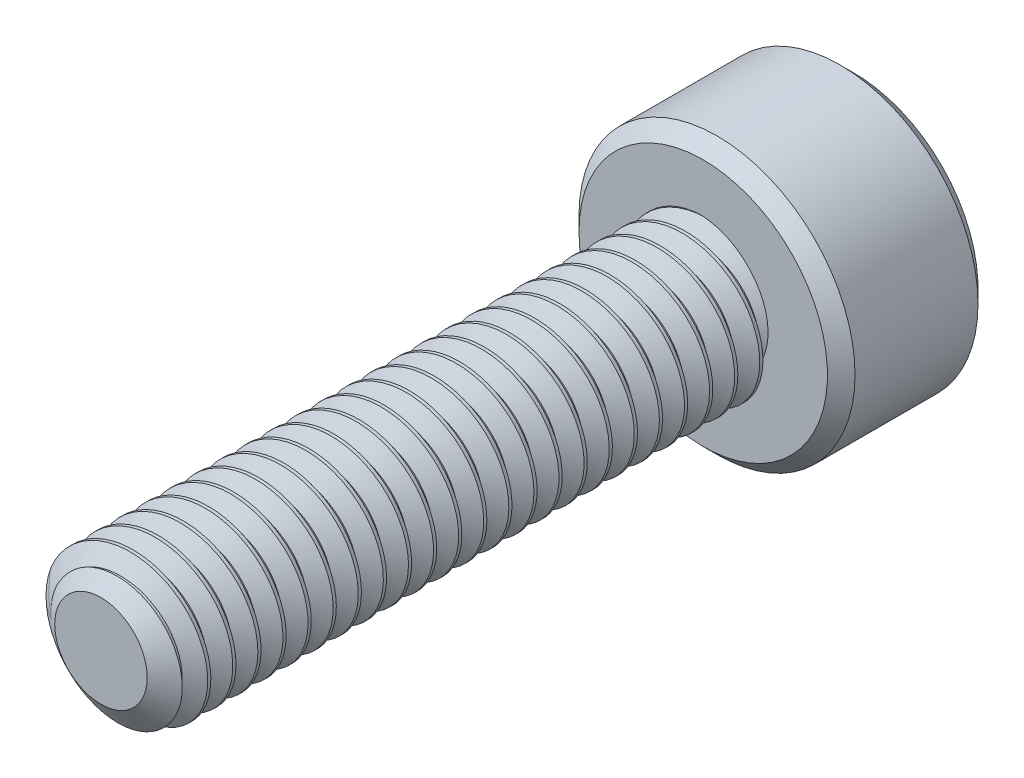
SolidWorks part; units mm, degrees
other "DetailItem1"
ref_plane "Front Plane" through (0, 0, 0) normal (0, 0, 1) x (1, 0, 0)
ref_plane "Top Plane" through (0, 0, 0) normal (0, 1, 0) x (1, 0, 0)
ref_plane "Right Plane" through (0, 0, 0) normal (1, 0, 0) x (0, 0, -1)
sketch "Sketch1" plane through (0, 0, 0) normal (0, 0, 1) x (1, 0, 0)
  circle A0 centre (0, 0) radius 1.5
  dimension "OD" = 3
extrude "Extrude1" add sketch "Sketch1" against normal blind 12
sketch "Sketch2" plane through (0, 0, 0) normal (0, 0, 1) x (1, 0, 0)
  circle A0 centre (0, 0) radius 1.5 construction
  circle A1 centre (0, 0) radius 1.5
curve "Helix/Spiral1" pitch 0.5 height 12.5 turns 25 parameters "pitch"=0.5
sketch "Sketch3" plane through (0, 0, 0) normal (1, 0, 0) x (0, 0, -1)
  line L0 (-0.4375, 1.5) -> (-0.25, 1.1752)
  line L1 (-0.25, 1.1752) -> (-0.1875, 1.1752)
  line L2 (-0.1875, 1.1752) -> (0, 1.5)
  line L3 (-0.4375, 1.5) -> (0, 1.5)
  line L4 (-0.2187, 1.5) -> (-0.2188, 1.1752) construction
  line L5 (-0.3438, 1.3376) -> (-0.0938, 1.3376) construction
  line L6 (0, 1.5) -> (0, -1.5) construction
  dimension "D1" = 0.0625
  dimension "D2" = 0.25
  dimension "D3" = 60
sweep "Cut-Sweep1" cut profiles "Sketch3" path "Helix/Spiral1"
sketch "Sketch4" plane through (0, 0, 0) normal (1, 0, 0) x (0, 0, -1)
  line L0 (0.4053, 1.5) -> (0, 0.9212)
  line L1 (0, 0.9212) -> (0, 1.5)
  line L2 (0.4053, 1.5) -> (0, 1.5)
  line L3 (-0.4375, 1.5) -> (0, 1.5) construction
  line L4 (0, 0) -> (7.0209, 0) construction
  dimension "D1" = 55
  dimension "D2" = 0.254
revolve "Cut-Revolve1" cut sketch "Sketch4" angle 360 about L4
sketch "Sketch6" plane through (0, 0, -12) normal (0, 0, -1) x (-1, 0, 0)
  circle A0 centre (0, 0) radius 2.75
  dimension "head dia" = 5.5
extrude "Extrude2" add sketch "Sketch6" along normal blind 3
sketch "Sketch7" plane through (0, 0, -15) normal (0, 0, -1) x (-1, 0, 0)
  line L1 (0, 1.4434) -> (-1.25, 0.7217)
  line L2 (-1.25, 0.7217) -> (-1.25, -0.7217)
  line L3 (-1.25, -0.7217) -> (0, -1.4434)
  line L4 (0, -1.4434) -> (1.25, -0.7217)
  line L5 (1.25, -0.7217) -> (1.25, 0.7217)
  line L6 (1.25, 0.7217) -> (0, 1.4434)
  circle A0 centre (0, 0) radius 1.25 construction
  dimension "hex dia" = 2.5
extrude "Cut-Extrude1" cut sketch "Sketch7" against normal blind 1.875
sketch "Sketch8" plane through (0, 0, -15) normal (0, 0, -1) x (-1, 0, 0)
  circle A0 centre (0, 0) radius 1.4434
extrude "Cut-Extrude2" cut sketch "Sketch8" against normal through all draft 45
chamfer "Chamfer1" distance 0.275 angle 45 2 edges at (-2.75, 0, -15) (-2.75, 0, -12)
sketch "Sketch10" plane through (0, 0, -12) normal (0, 0, 1) x (1, 0, 0)
  circle A1 centre (0, 0) radius 1.5
  circle A2 centre (0, 0) radius 1.5
  dimension "D1" = 0
ref_plane "Plane1" through (0, 0, 0) normal (0, 0, 1) x (1, 0, 0)
extrude "partial thread" [suppressed] add sketch "Sketch10" along normal up to surface (4 mm away) separate body
chamfer "Chamfer2" [suppressed] distance 0.06 angle 45
combine bodies "Combine1" [suppressed] operation type add bodies to combine 107 108
sketch "Sketch9" plane through (0, 0, 0) normal (1, 0, 0) x (0, 0, -1)
  line L0 (0, 1.5) -> (0, -1.5) construction
  line L1 (1.25, 1.5) -> (1.25, -1.5) construction
  dimension "D1" = 1.25
  dimension "D4" = 0.635
  dimension "D5" = 0.3302
equation "\"D3@Helix/Spiral1\" = \"screw length@Extrude1\"+\"pitch@Helix/Spiral1\""
equation "\"D1@Sketch3\" = \"pitch@Helix/Spiral1\"*.125"
equation "\"D2@Sketch3\" = \"pitch@Helix/Spiral1\"*.5"
equation "\"D1@Cut-Extrude1\" = \"hex dia@Sketch7\"*.75"
equation "\"D1@Chamfer1\" = \"head dia@Sketch6\"*.05"
equation "\"D1@Sketch9\" = \"pitch@Helix/Spiral1\"*2.5"
equation "\"D1@Chamfer2\"=\"OD@Sketch1\"*.02"
